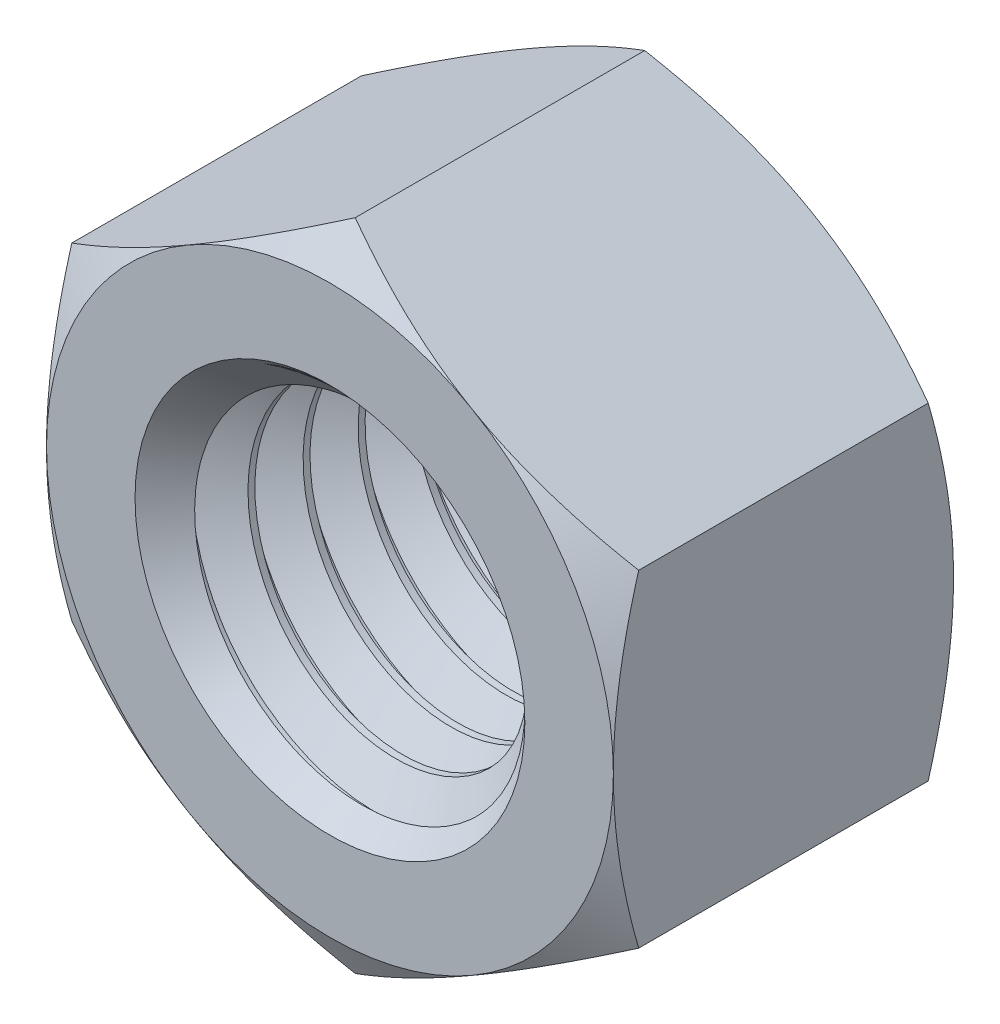
SolidWorks part; units mm, degrees
ref_plane "Front Plane" through (0, 0, 0) normal (0, 0, 1) x (1, 0, 0)
ref_plane "Top Plane" through (0, 0, 0) normal (0, 1, 0) x (1, 0, 0)
ref_plane "Right Plane" through (0, 0, 0) normal (1, 0, 0) x (0, 0, -1)
sketch "Sketch1" plane through (0, 0, 0) normal (0, 0, 1) x (1, 0, 0)
  line L1 (0, 10.3923) -> (-9, 5.1962)
  line L2 (-9, 5.1962) -> (-9, -5.1962)
  line L3 (-9, -5.1962) -> (0, -10.3923)
  line L4 (0, -10.3923) -> (9, -5.1962)
  line L5 (9, -5.1962) -> (9, 5.1962)
  line L6 (9, 5.1962) -> (0, 10.3923)
  circle A0 centre (0, 0) radius 9 construction
  dimension "Hex Width (S)" = 18
sketch "Sketch2" plane through (0, 0, 0) normal (1, 0, 0) x (0, 0, -1)
  line L0 (-5.4, 0) -> (5.4, 0) construction
  line L1 (-5.4, 0) -> (-5.4, 6)
  line L2 (-5.4, 6) -> (5.4, 6)
  line L3 (5.4, 6) -> (5.4, 0)
  line L4 (5.2906, 6.1894) -> (6.1656, 4.6739) construction
  line L5 (6.1656, 4.6739) -> (7.0406, 6.1894) construction
  line L6 (7.0406, 6.1894) -> (5.2906, 6.1894) construction
  line L7 (5.3453, 6.0947) -> (6.9859, 6.0947)
  line L8 (6.9859, 6.0947) -> (6.275, 4.8633)
  line L9 (6.275, 4.8633) -> (6.0562, 4.8633)
  line L10 (6.0562, 4.8633) -> (5.3453, 6.0947)
  line L11 (6.1656, 4.8633) -> (6.1656, 4.6739) construction
  line L12 (5.4, 6) -> (6.9312, 6) construction
  line L13 (6.1656, 6.1894) -> (6.1656, 6) construction
  line L14 (-5.4, -6) -> (5.4, -6)
  point P2 (0, 0)
  point P18 (6.1656, 6.0947)
  point P22 (-5.4, -6)
  dimension "Height (m)" = 10.8
  dimension "Thread Diameter" = 12
  dimension "Pitch (P)" = 1.75
  dimension "D2" = 0.2188
sketch "Sketch3" plane through (0, 0, 0) normal (0, 0, 1) x (1, 0, 0)
  line L0 (9, 5.1962) -> (0, 10.3923) construction
  line L1 (9, -5.1962) -> (9, 5.1962) construction
  line L2 (0, -10.3923) -> (9, -5.1962) construction
  line L3 (-9, -5.1962) -> (0, -10.3923) construction
  line L4 (-9, 5.1962) -> (-9, -5.1962) construction
  line L5 (0, 10.3923) -> (-9, 5.1962) construction
  line L6 (9, 5.1962) -> (0, 10.3923)
  line L7 (9, -5.1962) -> (9, 5.1962)
  line L8 (0, -10.3923) -> (9, -5.1962)
  line L9 (-9, -5.1962) -> (0, -10.3923)
  line L10 (-9, 5.1962) -> (-9, -5.1962)
  line L11 (0, 10.3923) -> (-9, 5.1962)
extrude "Boss-Extrude1" add sketch "Sketch3" along normal up to vertex (5.4 mm away) from vertex up to point (0, 0, 5.4) starting at point (0, 0, -5.4)
sketch "Sketch4" plane through (0, 0, 5.4) normal (0, 0, 1) x (1, 0, 0)
  circle A0 centre (0, 0) radius 9 construction
  circle A1 centre (0, 0) radius 9
extrude "Cut-Extrude1" cut sketch "Sketch4" against normal through all draft 60 flip side to cut
sketch "Sketch5" plane through (0, 0, -5.4) normal (0, 0, -1) x (-1, 0, 0)
  circle A0 centre (0, 0) radius 9 construction
  circle A1 centre (0, 0) radius 9
extrude "Cut-Extrude2" cut sketch "Sketch5" against normal through all draft 60 flip side to cut
sketch "Sketch6" plane through (0, 0, 0) normal (1, 0, 0) x (0, 0, -1)
  line L1 (-5.4, 0) -> (5.4, 0)
  line L2 (-5.4, 0) -> (-5.4, 6)
  line L3 (-5.4, 6) -> (5.4, 6)
  line L4 (5.4, 0) -> (5.4, 6)
revolve "Cut-Revolve1" cut sketch "Sketch6" angle 360 about L1
sketch "Sketch7" plane through (0, 0, -5.4) normal (0, 0, -1) x (-1, 0, 0)
  circle A0 centre (0, 0) radius 6 construction
  circle A1 centre (0, 0) radius 6
curve "Helix/Spiral1" pitch 1.75 height 12.55 radius 6 centre (0, 0, -5.4) axis (0, 0, 1) start towards (0, 1, 0)
sketch "Sketch8" plane through (0, 0, 0) normal (1, 0, 0) x (0, 0, -1)
  line L0 (5.3453, 6.0947) -> (6.9859, 6.0947) construction
  line L1 (6.0562, 4.8633) -> (5.3453, 6.0947) construction
  line L2 (6.275, 4.8633) -> (6.0562, 4.8633) construction
  line L3 (6.9859, 6.0947) -> (6.275, 4.8633) construction
  line L4 (5.3453, 6.0947) -> (6.9859, 6.0947)
  line L5 (6.0562, 4.8633) -> (5.3453, 6.0947)
  line L6 (6.275, 4.8633) -> (6.0562, 4.8633)
  line L7 (6.9859, 6.0947) -> (6.275, 4.8633)
sweep "Sweep1" add profiles "Sketch8" path "Helix/Spiral1"
sketch "Sketch9" plane through (0, 0, -5.4) normal (0, 0, -1) x (-1, 0, 0)
  circle A0 centre (0, 0) radius 6.1894
extrude "Cut-Extrude3" cut sketch "Sketch9" against normal through all draft 45 and the other way through all
sketch "Sketch10" plane through (0, 0, 5.4) normal (0, 0, 1) x (1, 0, 0)
  circle A1 centre (0, 0) radius 6.1894
  circle A2 centre (0, 0) radius 6.1894
  dimension "D1" = 0
extrude "Cut-Extrude4" cut sketch "Sketch10" against normal through all draft 45 and the other way through all
equation "\"D2@Sketch2\" = \"Pitch (P)@Sketch2\" / 8"
equation "\"D4@Helix/Spiral1\"=\"Pitch (P)@Sketch2\""
equation "\"D3@Helix/Spiral1\"=\"Height (m)@Sketch2\"+\"Pitch (P)@Sketch2\""
